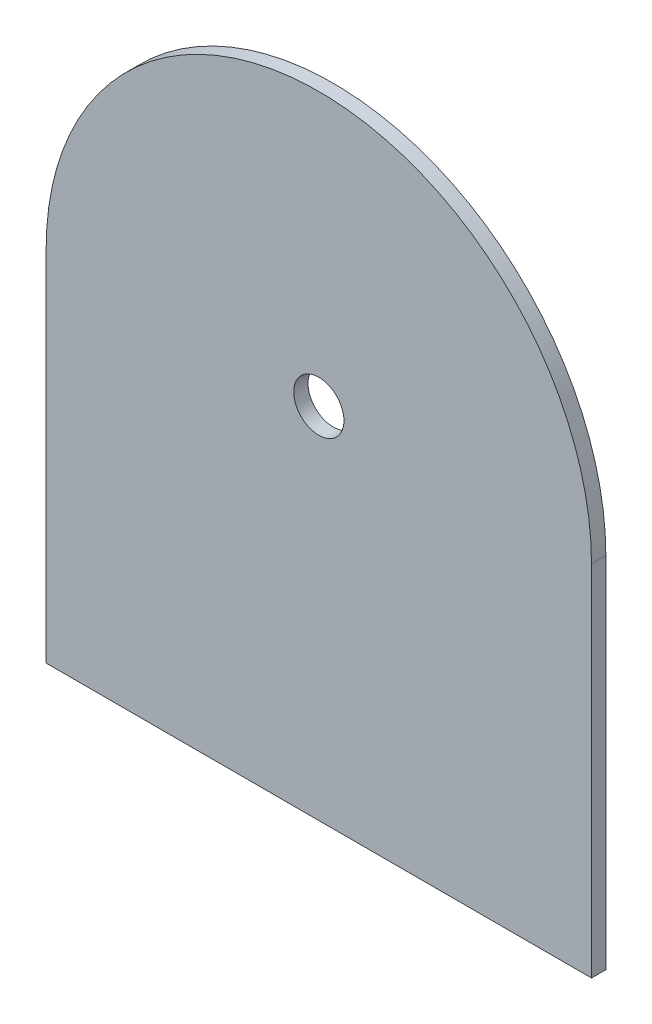
SolidWorks part; units mm, degrees
material "201 Annealed Stainless Steel (SS)"
ref_plane "Front Plane" through (0, 0, 0) normal (0, 0, 1) x (1, 0, 0)
ref_plane "Top Plane" through (0, 0, 0) normal (0, 1, 0) x (1, 0, 0)
ref_plane "Right Plane" through (0, 0, 0) normal (1, 0, 0) x (0, 0, -1)
sketch "Plate shape" plane through (0, 0, 0) normal (0, 0, 1) x (1, 0, 0)
  line L0 (-95, 0) -> (95, 0)
  line L1 (95, 0) -> (95, 125)
  line L2 (-95, 0) -> (-95, 125)
  line L3 (0, 30) -> (95, 30) construction
  arc A0 (-95, 125) -> (95, 125) centre (0, 125) cw
  arc A1 (95, 125) -> (-95, 125) centre (0, 125) cw construction
  point P3 (0, 0)
  dimension "D1" = 95
  dimension "D2" = 30
  dimension "D3" = 190
extrude "Outer casing" add sketch "Plate shape" along normal blind 5
sketch "Sketch1" plane through (0, 0, 5) normal (0, 0, 1) x (1, 0, 0)
  circle A0 centre (0, 125) radius 95 construction
  arc A1 (95, 125) -> (-95, 125) centre (0, 125) ccw construction
  circle A2 centre (0, 125) radius 8.75
  dimension "D1" = 17.5
extrude "Inner Cutout" cut sketch "Sketch1" against normal blind 10
